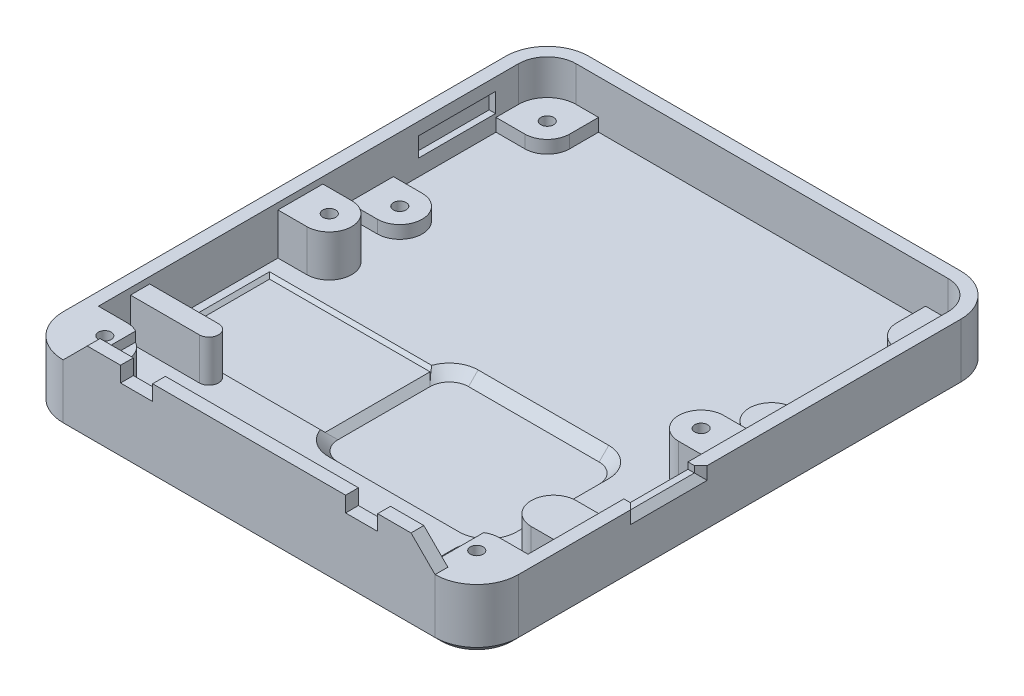
SolidWorks part; units mm, degrees
ref_plane "Front Plane" through (0, 0, 0) normal (0, 0, 1) x (1, 0, 0)
ref_plane "Top Plane" through (0, 0, 0) normal (0, 1, 0) x (1, 0, 0)
ref_plane "Right Plane" through (0, 0, 0) normal (1, 0, 0) x (0, 0, -1)
sketch "Sketch1" plane through (0, 0, 0) normal (0, 1, 0) x (1, 0, 0)
  line L0 (-33.8462, -25.5532) -> (31.1538, -25.5532)
  line L1 (-33.8462, 38.4468) -> (31.1538, 38.4468)
  line L2 (-33.8462, 38.4468) -> (-33.8462, 8.4468)
  line L3 (-33.8462, 8.4468) -> (31.1538, 8.4468)
  line L4 (31.1538, 38.4468) -> (31.1538, 8.4468)
  line L5 (-30.3462, 34.9468) -> (27.6538, 34.9468)
  line L6 (-30.3462, 34.9468) -> (-30.3462, 11.9468)
  line L7 (-30.3462, 11.9468) -> (27.6538, 11.9468)
  line L8 (27.6538, 34.9468) -> (27.6538, 11.9468)
  line L9 (-30.3462, 0.9468) -> (27.6538, 0.9468)
  line L10 (-30.3462, 0.9468) -> (-30.3462, -22.0532)
  line L11 (-33.8462, 4.4468) -> (31.1538, 4.4468)
  line L12 (-33.8462, 4.4468) -> (-33.8462, -25.5532)
  line L13 (-30.3462, -22.0532) -> (27.6538, -22.0532)
  line L14 (31.1538, 4.4468) -> (31.1538, -25.5532)
  line L15 (27.6538, 0.9468) -> (27.6538, -22.0532)
  line L16 (-37.9161, 25.3468) -> (-35.3276, 25.3468)
  line L17 (7.5538, 7.5472) -> (7.5538, 6.2645)
  line L18 (20.1538, 7.5472) -> (20.1538, 6.2645)
  dimension "D1" = 65
  dimension "D2" = 30
  dimension "D3" = 58
  dimension "D4" = 23
  dimension "D5" = 3.5
  dimension "D6" = 3.5
  dimension "D7" = 65
  dimension "D8" = 30
  dimension "D9" = 58
  dimension "D10" = 23
  dimension "D11" = 3.5
  dimension "D12" = 3.5
  dimension "D13" = 4
  dimension "D14" = 16.9
  dimension "D15" = 41.4
  dimension "D16" = 54
sketch "Sketch2" plane through (0, 0, 0) normal (0, 1, 0) x (1, 0, 0)
  line L0 (-33.8462, 38.4468) -> (-33.8462, 8.4468) construction
  line L1 (-30.3462, 39.4468) -> (27.6538, 39.4468)
  line L2 (-34.8462, 34.9468) -> (-34.8462, -34.0532)
  line L3 (-30.3462, -38.5532) -> (27.6538, -38.5532)
  line L4 (32.1538, 34.9468) -> (32.1538, -34.0532)
  line L5 (-33.8462, 38.4468) -> (31.1538, 38.4468) construction
  line L6 (31.1538, 38.4468) -> (31.1538, 8.4468) construction
  line L7 (-30.3462, 41.4468) -> (27.6538, 41.4468)
  line L8 (34.1538, 34.9468) -> (34.1538, -34.0532)
  line L9 (-30.3462, -40.5532) -> (27.6538, -40.5532)
  line L10 (-36.8462, 34.9468) -> (-36.8462, -34.0532)
  line L11 (-34.8462, 39.4468) -> (32.1538, 39.4468) construction
  line L12 (-34.8462, 39.4468) -> (-34.8462, -38.5532) construction
  line L13 (-36.8462, 41.4468) -> (-36.8462, -40.5532) construction
  line L14 (-36.8462, 41.4468) -> (34.1538, 41.4468) construction
  line L15 (32.1538, 39.4468) -> (32.1538, -38.5532) construction
  line L16 (34.1538, 41.4468) -> (34.1538, -40.5532) construction
  line L17 (-36.8462, -40.5532) -> (34.1538, -40.5532) construction
  line L18 (-34.8462, -38.5532) -> (32.1538, -38.5532) construction
  arc A0 (-30.3462, 39.4468) -> (-34.8462, 34.9468) centre (-30.3462, 34.9468) ccw
  arc A1 (-36.8462, 34.9468) -> (-30.3462, 41.4468) centre (-30.3462, 34.9468) cw
  arc A2 (32.1538, 34.9468) -> (27.6538, 39.4468) centre (27.6538, 34.9468) ccw
  arc A3 (34.1538, 34.9468) -> (27.6538, 41.4468) centre (27.6538, 34.9468) ccw
  arc A4 (27.6538, -40.5532) -> (34.1538, -34.0532) centre (27.6538, -34.0532) ccw
  arc A5 (-36.8462, -34.0532) -> (-30.3462, -40.5532) centre (-30.3462, -34.0532) ccw
  arc A6 (27.6538, -38.5532) -> (32.1538, -34.0532) centre (27.6538, -34.0532) ccw
  arc A7 (-30.3462, -38.5532) -> (-34.8462, -34.0532) centre (-30.3462, -34.0532) cw
  dimension "D6" = 4.5
  dimension "D7" = 6.5
  dimension "D8" = 4.5
  dimension "D9" = 6.5
  dimension "D10" = 6.5
  dimension "D11" = 4.5
  dimension "D1" = 1
  dimension "D2" = 1
  dimension "D3" = 1
  dimension "D4" = 78
  dimension "D5" = 2
extrude "Boss-Extrude1" add sketch "Sketch2" along normal blind 9.5
sketch "Sketch3" plane through (0, 0, 0) normal (0, 1, 0) x (1, 0, 0)
  line L0 (-30.3462, -38.5532) -> (27.6538, -38.5532)
  line L1 (-30.3462, 39.4468) -> (27.6538, 39.4468)
  line L2 (-34.8462, 34.9468) -> (-34.8462, -34.0532)
  line L4 (32.1538, 34.9468) -> (32.1538, -34.0532)
  arc A0 (-34.8462, -34.0532) -> (-30.3462, -38.5532) centre (-30.3462, -34.0532) ccw
  arc A1 (27.6538, -38.5532) -> (32.1538, -34.0532) centre (27.6538, -34.0532) ccw
  arc A2 (32.1538, 34.9468) -> (27.6538, 39.4468) centre (27.6538, 34.9468) ccw
  arc A3 (-30.3462, 39.4468) -> (-34.8462, 34.9468) centre (-30.3462, 34.9468) ccw
  point P15 (-34.8462, 39.4468)
  dimension "D1" = 4.5
  dimension "D2" = 4.5
extrude "Boss-Extrude2" add sketch "Sketch3" along normal blind 2
sketch "Sketch4" plane through (0, 2, 0) normal (0, 1, 0) x (1, 0, 0)
  line L1 (-4.1234, -3.5548) -> (16.2444, -3.5548)
  line L2 (-7.1234, -6.5548) -> (-7.1234, -20.9191)
  line L3 (-4.1234, -23.9191) -> (16.2444, -23.9191)
  line L4 (19.2444, -6.5548) -> (19.2444, -20.9191)
  arc A0 (16.2444, -23.9191) -> (19.2444, -20.9191) centre (16.2444, -20.9191) ccw
  arc A1 (-7.1234, -20.9191) -> (-4.1234, -23.9191) centre (-4.1234, -20.9191) ccw
  arc A2 (19.2444, -6.5548) -> (16.2444, -3.5548) centre (16.2444, -6.5548) ccw
  arc A3 (-7.1234, -6.5548) -> (-4.1234, -3.5548) centre (-4.1234, -6.5548) cw
  dimension "D1" = 3
extrude "Cut-Extrude2" cut sketch "Sketch4" against normal blind 1.5
chamfer "Chamfer1" distance 1.5 angle 45 8 edges at (6.0605, 2, 23.9191) (18.3657, 2, 23.0404) (-6.2447, 2, 23.0404) (19.2444, 2, 13.7369) (-7.1234, 2, 13.7369) (18.3657, 2, 4.4335) (-6.2447, 2, 4.4335) (6.0605, 2, 3.5548) tangent propagation no
sketch "Sketch5" plane through (0, 0.5, 0) normal (0, 1, 0) x (1, 0, 0)
  line L0 (-30.3462, 4.4468) -> (-34.8462, 4.4468)
  line L1 (-34.8462, 34.9468) -> (-34.8462, -34.0532) construction
  line L2 (-34.8462, 4.4468) -> (-34.8462, -2.5532)
  line L3 (-34.8462, -2.5532) -> (-30.3462, -2.5532)
  line L4 (27.6538, 4.4468) -> (32.1538, 4.4468)
  line L5 (32.1538, -34.0532) -> (32.1538, 34.9468) construction
  line L6 (32.1538, 4.4468) -> (32.1538, -2.5532)
  line L7 (32.1538, -34.0532) -> (32.1538, 34.9468) construction
  line L8 (32.1538, -2.5532) -> (27.6538, -2.5532)
  line L9 (32.1538, -18.5532) -> (32.1538, -25.5532)
  line L10 (-34.8462, -25.5532) -> (-24.1094, -25.5532)
  line L11 (-34.8462, -25.5532) -> (-34.8462, -22.5532)
  line L12 (-34.8462, -22.5532) -> (-24.1094, -22.5532)
  line L13 (32.1538, -25.5532) -> (27.6538, -25.5532)
  line L14 (27.6538, -18.5532) -> (32.1538, -18.5532)
  arc A0 (-30.3462, -2.5532) -> (-30.3462, 4.4468) centre (-30.3462, 0.9468) ccw
  arc A1 (27.6538, 4.4468) -> (27.6538, -2.5532) centre (27.6538, 0.9468) ccw
  arc A2 (-24.1094, -22.5532) -> (-24.1094, -25.5532) centre (-24.1094, -24.0532) cw
  arc A3 (27.6538, -18.5532) -> (27.6538, -25.5532) centre (27.6538, -22.0532) ccw
  dimension "D1" = 3
extrude "Boss-Extrude3" add sketch "Sketch5" along normal blind 8
sketch "Sketch6" plane through (0, 0.5, 0) normal (0, 1, 0) x (1, 0, 0)
  line L0 (-30.3462, 15.4468) -> (-34.8462, 15.4468)
  line L1 (-34.8462, 34.9468) -> (-34.8462, -34.0532) construction
  line L2 (-34.8462, 15.4468) -> (-34.8462, 8.4468)
  line L3 (-34.8462, 34.9468) -> (-34.8462, 4.4468) construction
  line L4 (-34.8462, 8.4468) -> (-30.3462, 8.4468)
  line L5 (-26.8462, 34.9468) -> (-26.8462, 39.4468)
  line L6 (27.6538, 39.4468) -> (-30.3462, 39.4468) construction
  line L7 (-26.8462, 39.4468) -> (-30.3462, 39.4468)
  line L8 (-30.3462, 31.4468) -> (-34.8462, 31.4468)
  line L9 (-34.8462, 31.4468) -> (-34.8462, 34.9468)
  line L10 (24.1538, 34.9468) -> (24.1538, 39.4468)
  line L11 (24.1538, 39.4468) -> (27.6538, 39.4468)
  line L12 (27.6538, 31.4468) -> (32.1538, 31.4468)
  line L13 (32.1538, 4.4468) -> (32.1538, 34.9468) construction
  line L14 (32.1538, 31.4468) -> (32.1538, 34.9468)
  line L15 (27.6538, 15.4468) -> (32.1538, 15.4468)
  line L16 (27.6538, 8.4468) -> (32.1538, 8.4468)
  line L17 (32.1538, -34.0532) -> (32.1538, 34.9468) construction
  line L18 (32.1538, 8.4468) -> (32.1538, 15.4468)
  arc A0 (-30.3462, 31.4468) -> (-26.8462, 34.9468) centre (-30.3462, 34.9468) ccw
  arc A1 (24.1538, 34.9468) -> (27.6538, 31.4468) centre (27.6538, 34.9468) ccw
  arc A2 (27.6538, 15.4468) -> (27.6538, 8.4468) centre (27.6538, 11.9468) ccw
  arc A3 (-30.3462, 8.4468) -> (-30.3462, 15.4468) centre (-30.3462, 11.9468) ccw
  arc A4 (-30.3462, 39.4468) -> (-34.8462, 34.9468) centre (-30.3462, 34.9468) ccw
  arc A5 (32.1538, 34.9468) -> (27.6538, 39.4468) centre (27.6538, 34.9468) ccw
  dimension "D1" = 4.5
  dimension "D2" = 4.5
extrude "Boss-Extrude4" add sketch "Sketch6" along normal blind 3.5
sketch "Sketch7" plane through (0, 0, 40.5532) normal (0, 0, 1) x (1, 0, 0)
  line L0 (27.6538, 9.5) -> (-30.3462, 9.5)
  line L1 (13.7046, 13.2512) -> (13.7046, 10.8512)
  line L2 (18.7046, 10.8512) -> (13.7046, 10.8512)
  line L3 (13.7046, 13.2512) -> (-16.3969, 13.2512)
  line L4 (-1.3462, 9.5) -> (-1.3462, 13.2512) construction
  line L5 (-30.3462, 9.5) -> (27.6538, 9.5) construction
  line L6 (-30.3462, 9.5) -> (-26.595, 13.2512)
  line L7 (-26.595, 13.2512) -> (-21.3969, 13.2512)
  line L8 (18.7046, 13.2512) -> (18.7046, 10.8512)
  line L9 (23.9027, 13.2512) -> (18.7046, 13.2512)
  line L10 (-21.3969, 13.2512) -> (-21.3969, 10.8512)
  line L11 (-21.3969, 10.8512) -> (-16.3969, 10.8512)
  line L12 (-16.3969, 13.2512) -> (-16.3969, 10.8512)
  line L13 (27.6538, 9.5) -> (23.9027, 13.2512)
  dimension "D1" = 5
extrude "Boss-Extrude5" add sketch "Sketch7" against normal up to vertex (2 mm away) up to point (-30.3462, 9.5, 38.5532)
sketch "Sketch10" plane through (0, 2, 0) normal (0, 1, 0) x (1, 0, 0)
  line L0 (-30.3462, -30.5532) -> (-34.8462, -30.5532)
  line L1 (27.6538, -30.5532) -> (32.1538, -30.5532)
  line L2 (-34.8462, -30.5532) -> (-34.8462, -34.0532)
  line L3 (-26.8462, -34.0532) -> (-26.8462, -38.5532)
  line L4 (32.1538, -34.0532) -> (32.1538, 34.9468) construction
  line L5 (-26.8462, -38.5532) -> (-30.3462, -38.5532)
  line L6 (32.1538, -30.5532) -> (32.1538, -34.0532)
  line L7 (24.1538, -34.0532) -> (24.1538, -38.5532)
  line L8 (-30.3462, -38.5532) -> (27.6538, -38.5532) construction
  line L9 (24.1538, -38.5532) -> (27.6538, -38.5532)
  arc A0 (-34.8462, -34.0532) -> (-30.3462, -38.5532) centre (-30.3462, -34.0532) ccw
  arc A1 (-26.8462, -34.0532) -> (-30.3462, -30.5532) centre (-30.3462, -34.0532) ccw
  arc A2 (32.1538, -34.0532) -> (27.6538, -38.5532) centre (27.6538, -34.0532) cw
  arc A3 (27.6538, -38.5532) -> (32.1538, -34.0532) centre (27.6538, -34.0532) ccw construction
  arc A4 (27.6538, -30.5532) -> (24.1538, -34.0532) centre (27.6538, -34.0532) ccw
extrude "Boss-Extrude6" add sketch "Sketch10" along normal up to vertex (7.5 mm away) up to point (-34.8462, 9.5, 34.0532)
sketch "Sketch11" plane through (34.1538, 0, 0) normal (1, 0, 0) x (0, 0, -1)
  line L0 (0.937, 8.5012) -> (-22.063, 8.5012) construction
  line L1 (-15.6062, 9.5013) -> (-5.6062, 9.5013)
  line L2 (-15.6062, 9.5013) -> (-15.6062, 8.5012)
  line L3 (-15.6062, 8.5012) -> (-5.6062, 8.5012)
  line L4 (-5.6062, 9.5013) -> (-5.6062, 8.5012)
extrude "Cut-Extrude3" cut sketch "Sketch11" against normal up to next
chamfer "Chamfer2" distance 1 angle 45 3 edges at (34.1538, 9.0006, 5.6062) (34.1538, 9.0006, 15.6062) (34.1538, 8.5012, 10.6062)
sketch "Sketch12" plane through (-34.8462, 0, 0) normal (-1, 0, 0) x (0, 0, 1)
  line L1 (-31.3878, 7.5452) -> (-19.3878, 7.5452)
  line L2 (-31.3878, 7.5452) -> (-31.3878, 4.5452)
  line L3 (-31.3878, 4.5452) -> (-19.3878, 4.5452)
  line L4 (-19.3878, 7.5452) -> (-19.3878, 4.5452)
  line L5 (-31.3878, 7.5452) -> (-19.3878, 4.5452) construction
  line L6 (-31.3878, 4.5452) -> (-19.3878, 7.5452) construction
  point P0 (-25.3878, 6.0452)
  dimension "D1" = 12
  dimension "D2" = 3
chamfer "Chamfer4" distance 1 angle 45 8 edges at (34.1538, 0, -0.4468) (32.25, 0, -39.543) (32.25, 0, 38.6493) (-1.3462, 0, -41.4468) (-1.3462, 0, 40.5532) (-34.9423, 0, -39.543) (-34.9423, 0, 38.6493) (-36.8462, 0, -0.4468)
hole_wizard "Ø2.0 (2) Diameter Hole1" positions "Sketch14" profile "Sketch13" hole size "Ø2.0" standard "ANSI Metric" end condition through all
sketch "Sketch14" plane through (0, 0, 0) normal (0, -1, 0) x (-1, 0, 0)
  point P0 (30.3462, -34.0532)
sketch "Sketch13" plane through (-30.3462, 0, 34.0532) normal (1, 0, 0) x (0, 0, -1)
  line L0 (0, 0) -> (0, 13.2512)
  line L1 (0, 13.2512) -> (1, 13.2512)
  line L2 (1, 13.2512) -> (1, 0)
  line L5 (1, 0) -> (0, 0)
  line L11 (0, -6.35) -> (0, 107.95) construction
  dimension "Thru Hole Dia." = 2
  dimension "Thru Hole Depth" = 13.2512
hole_wizard "Ø2.0 (2) Diameter Hole2" positions "Sketch16" profile "Sketch15" hole size "Ø2.0" standard "ANSI Metric" end condition through all
sketch "Sketch16" plane through (0, 0, 0) normal (0, -1, 0) x (-1, 0, 0)
  point P0 (-27.6538, -34.0532)
sketch "Sketch15" plane through (27.6538, 0, 34.0532) normal (1, 0, 0) x (0, 0, -1)
  line L0 (0, 0) -> (0, 13.2512)
  line L1 (0, 13.2512) -> (1, 13.2512)
  line L2 (1, 13.2512) -> (1, 0)
  line L5 (1, 0) -> (0, 0)
  line L11 (0, -6.35) -> (0, 107.95) construction
  dimension "Thru Hole Dia." = 2
  dimension "Thru Hole Depth" = 13.2512
hole_wizard "Ø2.0 (2) Diameter Hole3" positions "Sketch18" profile "Sketch17" hole size "Ø2.0" standard "ANSI Metric" end condition through all
sketch "Sketch18" plane through (0, 0, 0) normal (0, -1, 0) x (-1, 0, 0)
  point P0 (30.3462, 34.9468)
sketch "Sketch17" plane through (-30.3462, 0, -34.9468) normal (1, 0, 0) x (0, 0, -1)
  line L0 (0, 0) -> (0, 13.2512)
  line L1 (0, 13.2512) -> (1, 13.2512)
  line L2 (1, 13.2512) -> (1, 0)
  line L5 (1, 0) -> (0, 0)
  line L11 (0, -6.35) -> (0, 107.95) construction
  dimension "Thru Hole Dia." = 2
  dimension "Thru Hole Depth" = 13.2512
hole_wizard "Ø2.0 (2) Diameter Hole4" positions "Sketch20" profile "Sketch19" hole size "Ø2.0" standard "ANSI Metric" end condition through all
sketch "Sketch20" plane through (0, 0, 0) normal (0, -1, 0) x (-1, 0, 0)
  point P0 (-27.6538, 34.9468)
sketch "Sketch19" plane through (27.6538, 0, -34.9468) normal (1, 0, 0) x (0, 0, -1)
  line L0 (0, 0) -> (0, 13.2512)
  line L1 (0, 13.2512) -> (1, 13.2512)
  line L2 (1, 13.2512) -> (1, 0)
  line L5 (1, 0) -> (0, 0)
  line L11 (0, -6.35) -> (0, 107.95) construction
  dimension "Thru Hole Dia." = 2
  dimension "Thru Hole Depth" = 13.2512
hole_wizard "Ø2.0 (2) Diameter Hole5" positions "Sketch22" profile "Sketch21" hole size "Ø2.0" standard "ANSI Metric"
sketch "Sketch22" plane through (0, 8.5, 0) normal (0, 1, 0) x (1, 0, 0)
  point P0 (-30.3462, 0.9468)
sketch "Sketch21" plane through (-30.3462, 8.5, -0.9468) normal (1, 0, 0) x (0, 0, 1)
  line L0 (0, 0) -> (0, 6.5)
  line L1 (0, 6.5) -> (1, 6.5)
  line L2 (1, 6.5) -> (1, 0)
  line L5 (1, 0) -> (0, 0)
  line L10 (0, 6.5) -> (-1, 6.5) construction
  line L11 (0, -6.35) -> (0, 107.95) construction
  dimension "Hole Dia." = 2
  dimension "Hole Depth" = 6.5
  dimension "Drill Angle" = 180
hole_wizard "Ø2.0 (2) Diameter Hole6" positions "Sketch24" profile "Sketch25" hole size "Ø2.0" standard "ANSI Metric"
sketch "Sketch24" plane through (0, 8.5, 0) normal (0, 1, 0) x (1, 0, 0)
  point P0 (27.6538, 0.9468)
sketch "Sketch25" plane through (27.6538, 8.5, -0.9468) normal (1, 0, 0) x (0, 0, 1)
  line L0 (0, 0) -> (0, 6.5)
  line L1 (0, 6.5) -> (1, 6.5)
  line L2 (1, 6.5) -> (1, 0)
  line L5 (1, 0) -> (0, 0)
  line L10 (0, 6.5) -> (-1, 6.5) construction
  line L11 (0, -6.35) -> (0, 107.95) construction
  dimension "Hole Dia." = 2
  dimension "Hole Depth" = 6.5
  dimension "Drill Angle" = 180
hole_wizard "Ø2.0 (2) Diameter Hole7" positions "Sketch27" profile "Sketch26" hole size "Ø2.0" standard "ANSI Metric"
sketch "Sketch27" plane through (0, 4, 0) normal (0, 1, 0) x (1, 0, 0)
  point P0 (-30.3462, 11.9468)
sketch "Sketch26" plane through (-30.3462, 4, -11.9468) normal (1, 0, 0) x (0, 0, 1)
  line L0 (0, 0) -> (0, 3)
  line L1 (0, 3) -> (1, 3)
  line L2 (1, 3) -> (1, 0)
  line L5 (1, 0) -> (0, 0)
  line L10 (0, 3) -> (-1, 3) construction
  line L11 (0, -6.35) -> (0, 107.95) construction
  dimension "Hole Dia." = 2
  dimension "Hole Depth" = 3
  dimension "Drill Angle" = 180
hole_wizard "Ø2.0 (2) Diameter Hole8" positions "Sketch33" profile "Sketch32" hole size "Ø2.0" standard "ANSI Metric"
sketch "Sketch33" plane through (0, 4, 0) normal (0, 1, 0) x (1, 0, 0)
  point P0 (27.6538, 11.9468)
sketch "Sketch32" plane through (27.6538, 4, -11.9468) normal (1, 0, 0) x (0, 0, 1)
  line L0 (0, 0) -> (0, 3)
  line L1 (0, 3) -> (1, 3)
  line L2 (1, 3) -> (1, 0)
  line L5 (1, 0) -> (0, 0)
  line L10 (0, 3) -> (-1, 3) construction
  line L11 (0, -6.35) -> (0, 107.95) construction
  dimension "Hole Dia." = 2
  dimension "Hole Depth" = 3
  dimension "Drill Angle" = 180
sketch "Sketch34" plane through (0, 2, 0) normal (0, 1, 0) x (1, 0, 0)
  line L1 (-5.843, -6.5548) -> (-32.1578, -6.5548)
  line L2 (-5.843, -6.5548) -> (-5.843, -20.9191)
  line L3 (-5.843, -20.9191) -> (-32.1578, -20.9191)
  line L4 (-32.1578, -6.5548) -> (-32.1578, -20.9191)
extrude "Cut-Extrude5" cut sketch "Sketch34" against normal blind 0.5
chamfer "Chamfer5" distance 1.5 angle 45 3 edges at (-20.3906, 2, 20.9191) (-32.1578, 2, 13.7369) (-20.3906, 2, 6.5548)
extrude "Cut-Extrude6" cut sketch "Sketch12" along normal blind 1
sketch "Sketch35" plane through (0, 9.5, 0) normal (0, 1, 0) x (1, 0, 0)
  line L0 (-30.3462, -38.5532) -> (-26.8462, -38.5532) construction
  line L1 (-28.5962, -38.5532) -> (25.7783, -38.5532)
  line L2 (-28.5962, -38.5532) -> (-28.5962, -29.9744)
  line L3 (-28.5962, -29.9744) -> (25.7783, -29.9744)
  line L4 (25.7783, -38.5532) -> (25.7783, -29.9744)
extrude "Cut-Extrude7" cut sketch "Sketch35" against normal blind 1.5
sketch "Sketch36" plane through (0, 0, 0) normal (0, -1, 0) x (1, 0, 0)
  line L0 (-5.6411, -4.4361) -> (-6.5788, -2.9987)
  line L1 (-5.6135, -17.5484) -> (-6.5451, -18.9896)
  line L2 (2.8733, -4.4181) -> (3.8048, -2.9769)
  line L3 (2.9009, -17.5304) -> (3.8385, -18.9678)
  line L4 (-14.7411, -31.67) -> (-15.5841, -32.9742)
  line L5 (-9.464, -23.5056) -> (-10.3585, -24.8894)
  line L6 (-9.5167, 1.5049) -> (-10.4169, 2.885)
  line L7 (-14.8281, 9.647) -> (-15.6766, 10.9477)
  line L8 (12.0008, 9.7035) -> (12.8438, 11.0078)
  line L9 (6.7238, 1.5391) -> (7.6182, 2.9229)
  line L10 (6.7764, -23.4714) -> (7.6767, -24.8515)
  line L11 (12.0878, -31.6135) -> (12.9363, -32.9142)
  line L12 (-3.5903, -40.4468) -> (-2.2438, -13.3244)
  line L13 (0.898, -40.4468) -> (-0.192, -13.3244)
  line L14 (-3.5903, -40.4468) -> (0.898, -40.4468)
  line L15 (-2.2438, -13.3244) -> (-0.192, -13.3244)
  arc A0 (12.9363, -32.9142) -> (12.8438, 11.0078) centre (-1.3701, -10.9832) ccw
  arc A1 (12.0878, -31.6135) -> (12.0008, 9.7035) centre (-1.3701, -10.9832) ccw
  arc A2 (2.9009, -17.5304) -> (2.8733, -4.4181) centre (-1.3701, -10.9832) ccw
  arc A3 (3.8385, -18.9678) -> (3.8048, -2.9769) centre (-1.3701, -10.9832) ccw
  arc A4 (7.6767, -24.8515) -> (7.6182, 2.9229) centre (-1.3701, -10.9832) ccw
  arc A5 (6.7764, -23.4714) -> (6.7238, 1.5391) centre (-1.3701, -10.9832) ccw
  arc A6 (-15.6766, 10.9477) -> (-15.5841, -32.9742) centre (-1.3701, -10.9832) ccw
  arc A7 (-14.8281, 9.647) -> (-14.7411, -31.67) centre (-1.3701, -10.9832) ccw
  arc A8 (-10.4169, 2.885) -> (-10.3585, -24.8894) centre (-1.3701, -10.9832) ccw
  arc A9 (-9.5167, 1.5049) -> (-9.464, -23.5056) centre (-1.3701, -10.9832) ccw
  arc A10 (-6.5788, -2.9987) -> (-6.5451, -18.9896) centre (-1.3701, -10.9832) ccw
  arc A11 (-5.6411, -4.4361) -> (-5.6135, -17.5484) centre (-1.3701, -10.9832) ccw
extrude "Cut-Extrude8" cut sketch "Sketch36" against normal blind 0.4
sketch "Sketch37" plane through (0, 0, 0) normal (0, 1, 0) x (1, 0, 0)
  line L0 (-1.9008, 5.7134) -> (12.3211, -8.0776)
  line L1 (12.3211, -8.0776) -> (16.1409, -4.1385)
  line L2 (16.1409, -4.1385) -> (3.4609, 11.2426)
  line L3 (3.4609, 11.2426) -> (9.8009, 20.3663)
  line L4 (9.8009, 20.3663) -> (15.1149, 16.2462)
  line L5 (15.1149, 16.2462) -> (17.8041, 19.0194)
  line L6 (17.8041, 19.0194) -> (12.774, 24.201)
  line L7 (12.774, 24.201) -> (13.7731, 25.4896)
  line L8 (13.7731, 25.4896) -> (13.4862, 25.712)
  line L9 (-1.9008, 5.7134) -> (-4.5225, 3.5521)
  line L10 (-4.5225, 3.5521) -> (-6.7547, 2.0307)
  line L11 (-6.7547, 2.0307) -> (-8.3897, 1.1526)
  line L12 (-8.3897, 1.1526) -> (-9.0215, 1.5916)
  line L13 (-9.0215, 1.5916) -> (-9.9767, 1.0787)
  line L14 (-9.9767, 1.0787) -> (-10.839, 0.7913)
  line L15 (-10.839, 0.7913) -> (-11.0799, 0.7913)
  line L16 (13.4862, 25.712) -> (-11.0799, 0.7913) construction
  line L17 (-11.0833, 1.0321) -> (-11.0799, 0.7913)
  line L18 (-10.8083, 1.8985) -> (-11.0833, 1.0321)
  line L19 (-10.3091, 2.8609) -> (-10.8083, 1.8985)
  line L20 (-10.7571, 3.4863) -> (-10.3091, 2.8609)
  line L21 (-9.9026, 5.1337) -> (-10.7571, 3.4863)
  line L22 (-8.4134, 7.3875) -> (-9.9026, 5.1337)
  line L23 (-6.2899, 10.0399) -> (-8.4134, 7.3875)
  line L24 (13.2596, 25.9958) -> (13.4862, 25.712)
  line L25 (11.9855, 24.9783) -> (13.2596, 25.9958)
  line L26 (6.7323, 29.9336) -> (11.9855, 24.9783)
  line L27 (3.9979, 27.2049) -> (6.7323, 29.9336)
  line L28 (8.1938, 21.9505) -> (3.9979, 27.2049)
  line L29 (-0.8381, 15.4803) -> (8.1938, 21.9505)
  line L30 (-16.3994, 27.9385) -> (-0.8381, 15.4803)
  line L31 (-20.2833, 24.0627) -> (-16.3994, 27.9385)
  line L32 (-6.2899, 10.0399) -> (-20.2833, 24.0627)
extrude "Cut-Extrude14" cut sketch "Sketch37" along normal blind 0.4
